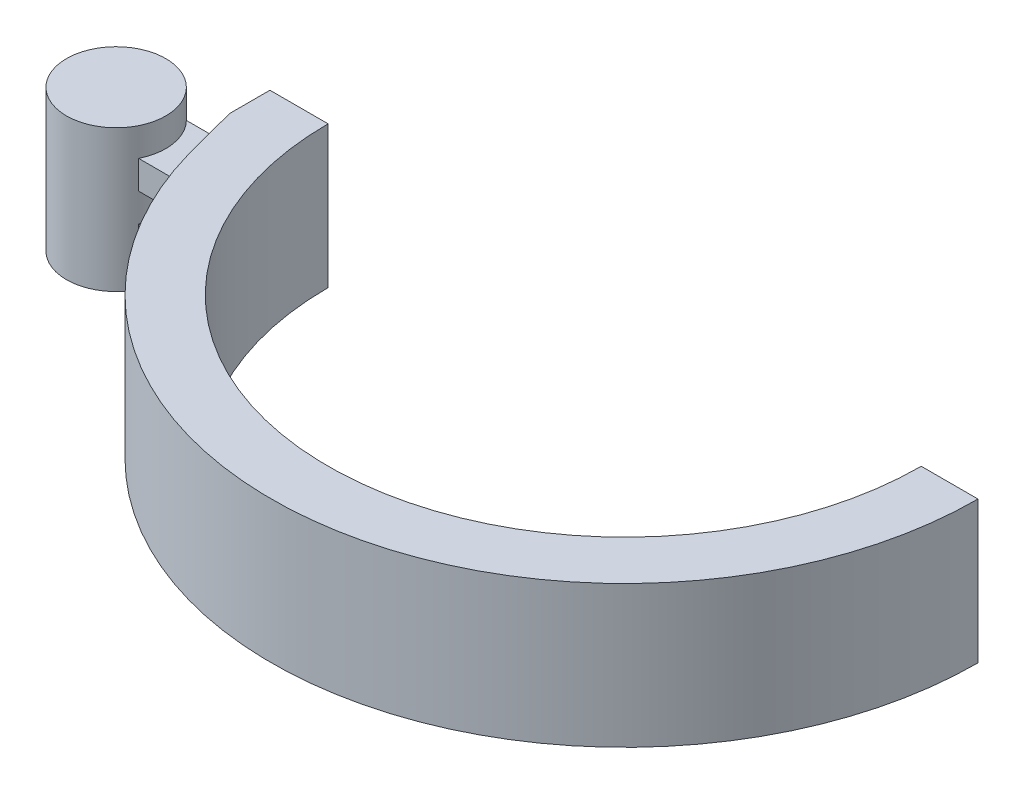
SolidWorks part; units mm, degrees
ref_plane "Front Plane" through (0, 0, 0) normal (0, 0, 1) x (1, 0, 0)
ref_plane "Top Plane" through (0, 0, 0) normal (0, 1, 0) x (1, 0, 0)
ref_plane "Right Plane" through (0, 0, 0) normal (1, 0, 0) x (0, 0, -1)
sketch "Sketch2" plane through (0, 0, 0) normal (0, 1, 0) x (1, 0, 0)
  line L0 (2.8, 2.6181) -> (25.75, 2.6181) construction
  line L1 (2.8, 2.6181) -> (2.8, 1.2247)
  line L2 (2.8, 2.6181) -> (4.85, 2.6181)
  line L5 (1.5689, -0.7753) -> (3.3214, -0.7753)
  line L6 (3.3214, -0.7753) -> (3.3214, -0.7753)
  line L7 (25.75, 2.6181) -> (27.75, 2.6181)
  line L8 (3.3214, -0.7753) -> (3.3214, -0.7753)
  line L10 (1.25, -0.7753) -> (3.3214, -0.7753) construction
  line L14 (1.25, 1.2247) -> (2.8, 1.2247)
  circle A0 centre (0, 0) radius 1.75
  arc A4 (4.85, 2.6181) -> (25.75, 2.6181) centre (15.3, 2.6181) ccw
  arc A5 (3.3214, -0.7753) -> (27.75, 2.6181) centre (15.3, 2.6181) ccw
  dimension "D1" = 3.5
  dimension "D2" = 2.05
  dimension "D3" = 10.45
  dimension "D4" = 2
  dimension "D5" = 15.3
  dimension "D6" = 2.6181
  dimension "D9" = 1.55
extrude "Boss-Extrude2" add sketch "Sketch2" along normal blind 5 contours A0 | A0 region at (3.825, 0, -2.3253) region at (0, 0, 0)
sketch "Sketch6" plane through (0, 5, 0) normal (0, 1, 0) x (1, 0, 0)
  line L0 (2.8, 1.2247) -> (1.25, 1.2247)
  line L1 (3.3214, -0.7753) -> (1.5689, -0.7753)
  arc A0 (1.5689, -0.7753) -> (1.25, 1.2247) centre (0, 0) ccw
  arc A1 (1.25, 1.2247) -> (1.5689, -0.7753) centre (0, 0) ccw construction
  arc A2 (2.8, 1.2247) -> (3.3214, -0.7753) centre (50.5741, 12.6107) ccw
  dimension "D1" = 49.1122
extrude "Cut-Extrude1" cut sketch "Sketch6" against normal blind 1
sketch "Sketch8" plane through (0, 4, 0) normal (0, 1, 0) x (1, 0, 0)
  line L0 (2.8, 1.2247) -> (1.25, 1.2247)
  line L1 (1.5689, -0.7753) -> (3.3214, -0.7753)
  arc A0 (1.25, 1.2247) -> (1.5689, -0.7753) centre (0, 0) cw
  arc A1 (2.8, 1.2247) -> (3.3214, -0.7753) centre (50.5741, 12.6107) ccw
  dimension "D1" = 49.1122
extrude "Cut-Extrude2" cut sketch "Sketch8" against normal blind 1 from offset 1 offset against normal yes
sketch "Sketch9" plane through (0, 2, 0) normal (0, 1, 0) x (1, 0, 0)
  line L0 (2.8, 1.2247) -> (1.25, 1.2247)
  line L1 (3.3214, -0.7753) -> (1.5689, -0.7753)
  arc A0 (1.25, 1.2247) -> (1.5689, -0.7753) centre (0, 0) cw
  arc A1 (2.8, 1.2247) -> (3.3214, -0.7753) centre (50.5741, 12.6107) ccw
  dimension "D1" = 49.1122
extrude "Cut-Extrude3" cut sketch "Sketch9" against normal blind 1 from offset 1 offset against normal yes
